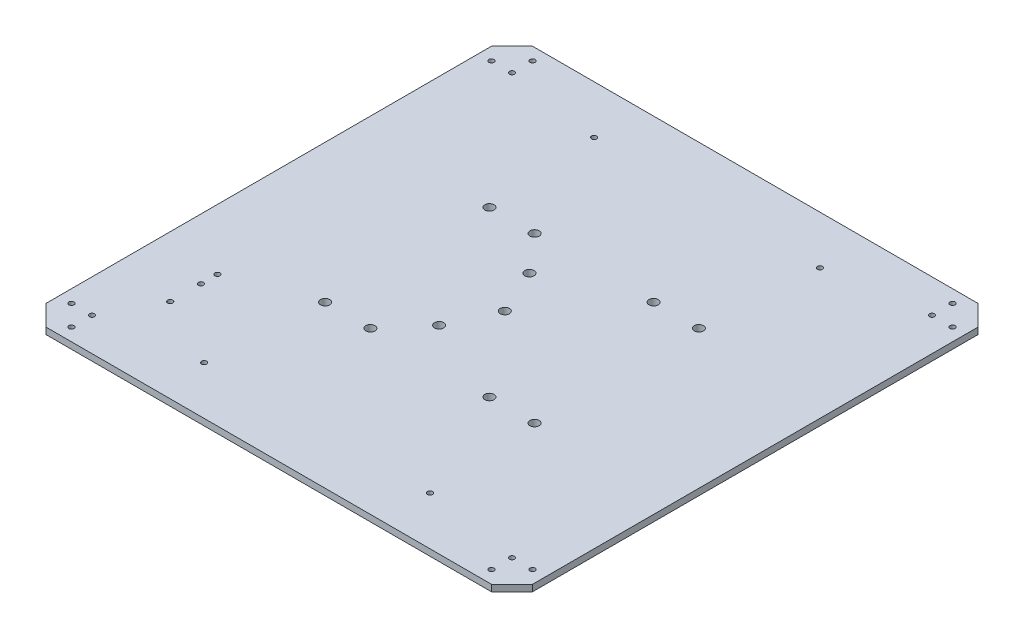
SolidWorks part; units mm, degrees
material "6061-T6 (SS)"
ref_plane "Front Plane" through (0, 0, 0) normal (0, 0, 1) x (1, 0, 0)
ref_plane "Top Plane" through (0, 0, 0) normal (0, 1, 0) x (1, 0, 0)
ref_plane "Right Plane" through (0, 0, 0) normal (1, 0, 0) x (0, 0, -1)
sketch "Sketch1" plane through (0, 0, 0) normal (0, 1, 0) x (1, 0, 0)
  line L0 (-118.5, 118.5) -> (118.5, -118.5) construction
  line L1 (-108.5, 118.5) -> (108.5, 118.5)
  line L2 (-118.5, 108.5) -> (-118.5, -108.5)
  line L3 (-108.5, -118.5) -> (108.5, -118.5)
  line L4 (118.5, 108.5) -> (118.5, -108.5)
  line L5 (108.5, -118.5) -> (118.5, -108.5)
  line L6 (108.5, 118.5) -> (118.5, 108.5)
  line L7 (-118.5, 108.5) -> (-108.5, 118.5)
  line L8 (-118.5, -108.5) -> (-108.5, -118.5)
  point P2 (-118.5, -118.5)
  point P3 (118.5, 118.5)
  dimension "D1" = 237
  dimension "D2" = 237
extrude "Boss-Extrude1" add sketch "Sketch1" along normal blind 3.175
sketch "Sketch2" plane through (0, 3.175, 0) normal (0, 1, 0) x (1, 0, 0)
  circle A0 centre (-51, -40) radius 1.5
  circle A2 centre (-29, -40) radius 2.25
  circle A5 centre (-51, 40) radius 1.5
  circle A6 centre (-29, 40) radius 2.25
  circle A9 centre (29, 40) radius 2.25
  circle A10 centre (51, 40) radius 2.25
  circle A14 centre (29, -40) radius 2.25
  circle A15 centre (51, -40) radius 2.25
  circle A16 centre (-3.5, 0) radius 2.25
  circle A17 centre (-13.5, 22) radius 2.25
  circle A18 centre (-13.5, -22) radius 2.25
  dimension "D1" = 3
  dimension "D2" = 4.5
extrude "Cut-Extrude1" cut sketch "Sketch2" against normal through all
hole_wizard "M3x0.5 Tapped Hole1" positions "Sketch4" profile "Sketch3" tap size "M3x0.5" standard "Ansi Metric" end condition through all
sketch "Sketch4" plane through (0, 3.175, 0) normal (0, 1, 0) x (-1, 0, 0)
  line L0 (108.5, 118.5) -> (-108.5, 118.5) construction
  line L1 (118.5, -108.5) -> (118.5, 108.5) construction
  line L2 (-108.5, -118.5) -> (108.5, -118.5) construction
  line L3 (-118.5, 108.5) -> (-118.5, -108.5) construction
  point P0 (112.3, -102.3)
  point P1 (102.3, -112.3)
  point P3 (-102.3, -112.3)
  point P5 (-112.3, -102.3)
  point P7 (-112.3, 102.3)
  point P9 (-102.3, 112.3)
  point P11 (102.3, 112.3)
  point P13 (112.3, 102.3)
  point P32 (-102.3, 102.3)
  point P34 (-102.3, -102.3)
  point P36 (102.3, -102.3)
  point P38 (102.3, 102.3)
  dimension "D1" = 16.2
  dimension "D2" = 6.2
  dimension "D3" = 6.2
  dimension "D4" = 16.2
  dimension "D5" = 16.2
  dimension "D6" = 6.2
  dimension "D7" = 6.2
  dimension "D8" = 16.2
sketch "Sketch3" plane through (-112.3, 3.175, -102.3) normal (1, 0, 0) x (0, 0, 1)
  line L0 (0, 0) -> (0, 3.175)
  line L1 (0, 3.175) -> (1.25, 3.175)
  line L2 (1.25, 3.175) -> (1.25, 0)
  line L5 (1.25, 0) -> (0, 0)
  line L11 (0, -6.35) -> (0, 107.95) construction
  dimension "Thru Tap Drill Dia." = 2.5
  dimension "Thru Tap Drill Depth" = 3.175
cosmetic thread "Hole Thread1" parameters "D2"=3
cosmetic thread "Hole Thread2" parameters "D2"=3
cosmetic thread "Hole Thread3" parameters "D2"=3
cosmetic thread "Hole Thread4" parameters "D2"=3
cosmetic thread "Hole Thread5" parameters "D2"=3
cosmetic thread "Hole Thread6" parameters "D2"=3
cosmetic thread "Hole Thread7" parameters "D2"=3
cosmetic thread "Hole Thread8" parameters "D2"=3
cosmetic thread "Hole Thread9" parameters "D2"=3
cosmetic thread "Hole Thread10" parameters "D2"=3
cosmetic thread "Hole Thread11" parameters "D2"=3
cosmetic thread "Hole Thread12" parameters "D2"=3
sketch "Sketch5" plane through (0, 3.175, 0) normal (0, 1, 0) x (1, 0, 0)
  circle A0 centre (-55, 95) radius 1.25
  circle A1 centre (55, 95) radius 1.25
  circle A2 centre (-55, -95) radius 1.25
  circle A3 centre (55, -95) radius 1.25
  dimension "D1" = 2.5
extrude "Cut-Extrude2" cut sketch "Sketch5" against normal through all
sketch "Sketch6" plane through (0, 3.175, 0) normal (0, 1, 0) x (1, 0, 0)
  line L0 (-108.5, -118.5) -> (108.5, -118.5) construction
  line L1 (-118.5, 108.5) -> (-118.5, -108.5) construction
  circle A0 centre (-89, -62.5) radius 1.25
  circle A1 centre (-89, -54.5) radius 1.25
  circle A2 centre (-89, -77.5) radius 1.25
  dimension "D3" = 2.5
  dimension "D1" = 56
  dimension "D2" = 29.5
  dimension "D4" = 8
  dimension "D5" = 15
extrude "Cut-Extrude3" cut sketch "Sketch6" against normal blind 10
hole_wizard "M4 Clearance Hole1" positions "Sketch8" profile "Sketch7" hole size "M4" standard "ANSI Metric"
sketch "Sketch8" plane through (0, 3.175, 0) normal (0, 1, 0) x (-1, 0, 0)
  point P0 (51, -40)
  point P1 (51, 40)
sketch "Sketch7" plane through (-51, 3.175, -40) normal (1, 0, 0) x (0, 0, 1)
  line L0 (0, 0) -> (0, 11.3519)
  line L1 (0, 11.3519) -> (2.25, 10)
  line L2 (2.25, 10) -> (2.25, 0)
  line L5 (2.25, 0) -> (0, 0)
  line L10 (0, 11.3519) -> (-2.25, 10) construction
  line L11 (0, -6.35) -> (0, 107.95) construction
  dimension "Hole Dia." = 4.5
  dimension "Hole Depth" = 10
  dimension "Drill Angle" = 118
